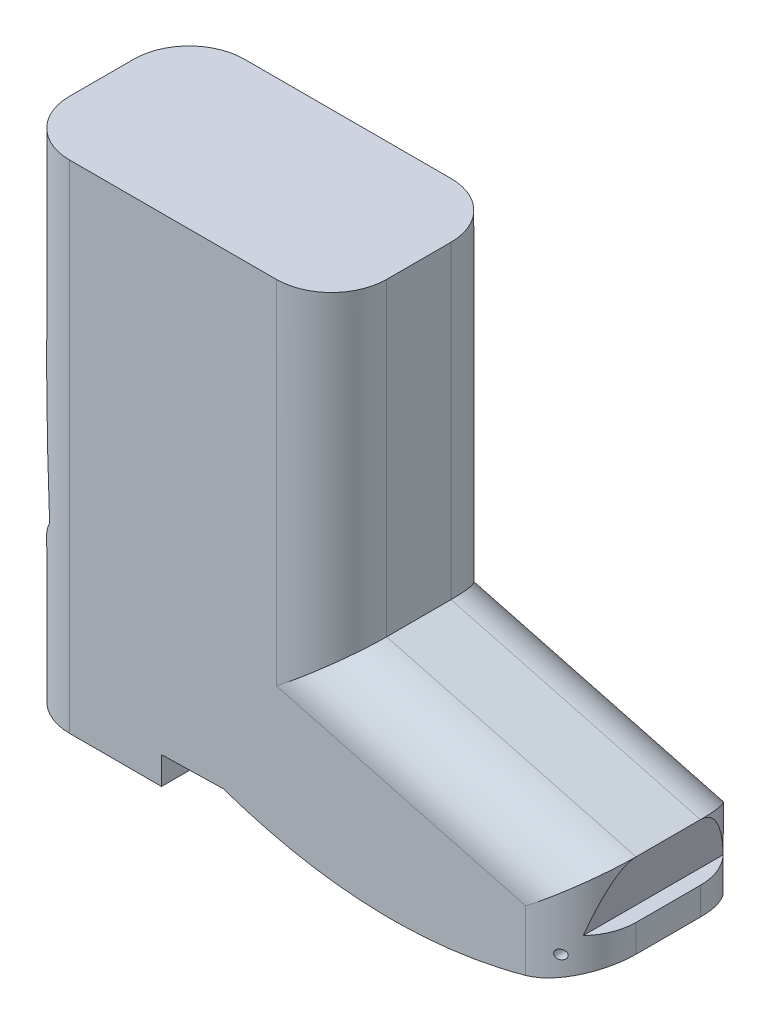
SolidWorks part; units mm, degrees
ref_plane "Front Plane" through (0, 0, 0) normal (0, 0, 1) x (1, 0, 0)
ref_plane "Top Plane" through (0, 0, 0) normal (0, 1, 0) x (1, 0, 0)
ref_plane "Right Plane" through (0, 0, 0) normal (1, 0, 0) x (0, 0, -1)
sketch "Sketch1" plane through (0, 0, 0) normal (0, 1, 0) x (1, 0, 0)
  line L1 (-308, 47.5) -> (0, 47.5)
  line L2 (-308, 47.5) -> (-308, -47.5)
  line L3 (-308, -47.5) -> (0, -47.5)
  line L4 (0, 47.5) -> (0, -47.5)
  point P4 (0, 0)
  dimension "D1" = 308
  dimension "D2" = 95
extrude "Boss-Extrude1" add sketch "Sketch1" along normal blind 270
fillet "Fillet1" radius 30 4 edges at (-308, 135, -47.5) (-308, 135, 47.5) (0, 135, -47.5) (0, 135, 47.5)
sketch "Sketch2" plane through (0, 0, 47.5) normal (0, 0, 1) x (1, 0, 0)
  line L0 (-278, 0) -> (-30, 0) construction
  line L1 (-228, 0) -> (-228, 15)
  line L2 (-228, 15) -> (-108, 0) construction
  line L3 (-108, 0) -> (0, 20) construction
  line L4 (0, 20) -> (0, 35)
  line L5 (0, 270) -> (0, 0) construction
  line L6 (0, 35) -> (-8.1568, 35)
  line L7 (-8.1568, 35) -> (0, 65.8977)
  line L8 (0, 65.8977) -> (-135.5947, 101.694)
  line L9 (-135.5947, 101.694) -> (-135.5947, 270)
  line L10 (-278, 270) -> (-30, 270) construction
  line L11 (-135.5947, 270) -> (-310, 270)
  line L12 (-310, 270) -> (-292.6954, 89.8188)
  line L13 (-292.6954, 89.8188) -> (-308, 65.7084)
  line L14 (-50, 0) -> (-50, 5) construction
  line L15 (-308, 65.7084) -> (-308, 0)
  line L16 (-308, 0) -> (-228, 0)
  line L17 (-278, 0) -> (-30, 0) construction
  spline S0 degree 2 poles (-228, 15) (-211.2296, 15.3678) (-194.4593, 15.7355) knots 0 0 0 0.147108 0.147108 0.147108
  spline S1 degree 2 poles (-194.4593, 15.7355) (-97.1746, -17.8345) (0, 20) knots 0 0 0 1 1 1
  point P7 (-308, 32.8542)
  dimension "D1" = 200
  dimension "D2" = 15
  dimension "D3" = 308
  dimension "D4" = 15
  dimension "D5" = 20
  dimension "D6" = 80
  dimension "D7" = 50
  dimension "D8" = 5
extrude "Cut-Extrude1" cut sketch "Sketch2" against normal through all flip side to cut
fillet "Fillet2" radius 30 4 edges at (-82.7973, 87.7558, -47.5) (-82.7973, 87.7558, 47.5) (-135.5947, 185.847, -47.5) (-135.5947, 185.847, 47.5)
sketch "Sketch3" plane through (0, 0, 0) normal (0, 0, 1) x (1, 0, 0)
  line L0 (-278, 0) -> (-226.7249, 0) construction
  line L1 (0, 35) -> (0, 20) construction
  circle A0 centre (-15, 25.4) radius 2.5
  dimension "D1" = 5
  dimension "D2" = 25.4
  dimension "D3" = 15
extrude "Cut-Extrude2" cut sketch "Sketch3" against normal through all both and the other way through all
